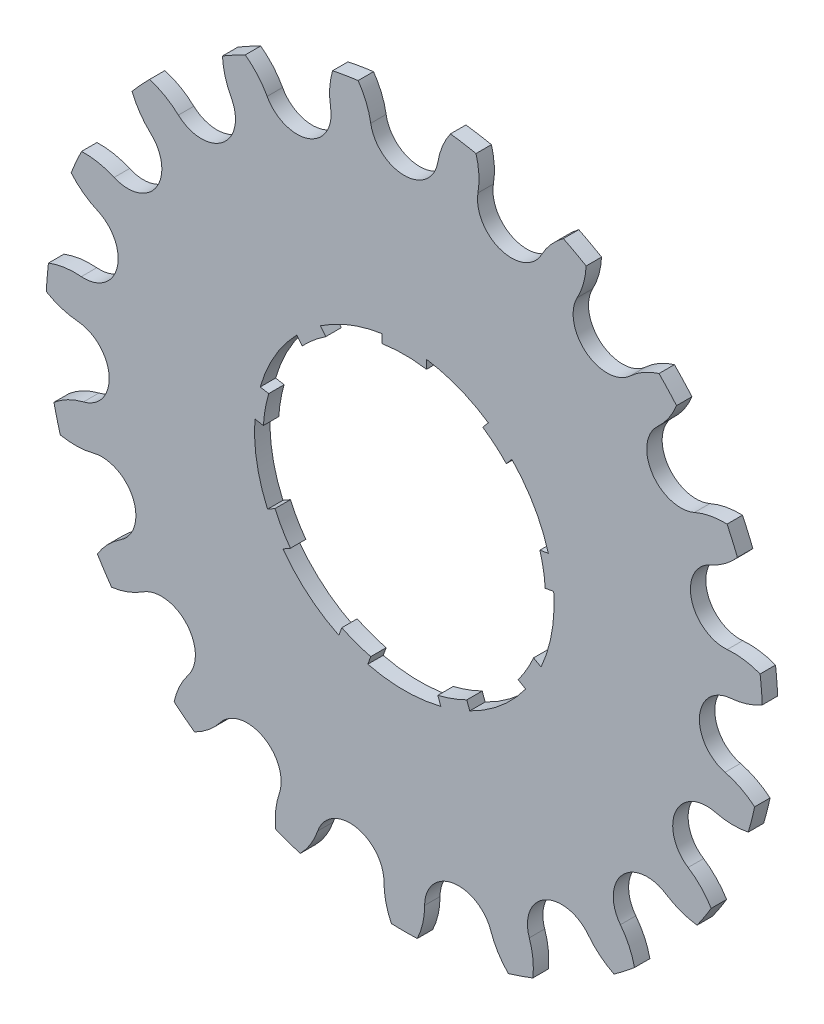
SolidWorks part; units mm, degrees
ref_plane "Alzado" through (0, 0, 0) normal (0, 0, 1) x (1, 0, 0)
ref_plane "Planta" through (0, 0, 0) normal (0, 1, 0) x (1, 0, 0)
ref_plane "Vista lateral" through (0, 0, 0) normal (1, 0, 0) x (0, 0, -1)
sketch "Sk_Disco" plane through (0, 0, 0) normal (0, 0, 1) x (1, 0, 0)
  line L0 (2.6, 17.3058) -> (2.6, 16.2939)
  line L1 (-2.6, 16.2939) -> (-2.6, 17.3058)
  line L2 (-9.8102, 14.4917) -> (-9.1638, 13.7213)
  line L3 (-11.9216, 11.4073) -> (-12.568, 12.1777)
  line L4 (-16.8302, 4.7954) -> (-15.8398, 4.6207)
  line L5 (-16.4649, 1.0754) -> (-17.4553, 1.2501)
  line L6 (-15.9751, -7.1447) -> (-15.1041, -6.6419)
  line L7 (-13.3041, -9.7596) -> (-14.1751, -10.2624)
  line L8 (-7.6451, -15.7418) -> (-7.3011, -14.7968)
  line L9 (-3.9182, -16.028) -> (-4.2622, -16.973)
  line L10 (4.2622, -16.973) -> (3.9182, -16.028)
  line L11 (7.3011, -14.7968) -> (7.6451, -15.7418)
  line L12 (14.1751, -10.2624) -> (13.3041, -9.7596)
  line L13 (15.1041, -6.6419) -> (15.9751, -7.1447)
  line L14 (17.4553, 1.2501) -> (16.4649, 1.0754)
  line L15 (15.8398, 4.6207) -> (16.8302, 4.7954)
  line L16 (12.568, 12.1777) -> (11.9216, 11.4073)
  line L17 (9.1638, 13.7213) -> (9.8102, 14.4917)
  circle A0 centre (0, 0) radius 41.8635
  arc A1 (2.6, 16.2939) -> (-2.6, 16.2939) centre (0, 0) ccw
  arc A2 (-2.6, 17.3058) -> (-9.8102, 14.4917) centre (0, 0) ccw
  arc A3 (-9.1638, 13.7213) -> (-11.9216, 11.4073) centre (0, 0) ccw
  arc A4 (-12.568, 12.1777) -> (-16.8302, 4.7954) centre (0, 0) ccw
  arc A5 (-15.8398, 4.6207) -> (-16.4649, 1.0754) centre (0, 0) ccw
  arc A6 (-17.4553, 1.2501) -> (-15.9751, -7.1447) centre (0, 0) ccw
  arc A7 (-15.1041, -6.6419) -> (-13.3041, -9.7596) centre (0, 0) ccw
  arc A8 (-14.1751, -10.2624) -> (-7.6451, -15.7418) centre (0, 0) ccw
  arc A9 (-7.3011, -14.7968) -> (-3.9182, -16.028) centre (0, 0) ccw
  arc A10 (-4.2622, -16.973) -> (4.2622, -16.973) centre (0, 0) ccw
  arc A11 (3.9182, -16.028) -> (7.3011, -14.7968) centre (0, 0) ccw
  arc A12 (7.6451, -15.7418) -> (14.1751, -10.2624) centre (0, 0) ccw
  arc A13 (13.3041, -9.7596) -> (15.1041, -6.6419) centre (0, 0) ccw
  arc A14 (15.9751, -7.1447) -> (17.4553, 1.2501) centre (0, 0) ccw
  arc A15 (16.4649, 1.0754) -> (15.8398, 4.6207) centre (0, 0) ccw
  arc A16 (16.8302, 4.7954) -> (12.568, 12.1777) centre (0, 0) ccw
  arc A17 (11.9216, 11.4073) -> (9.1638, 13.7213) centre (0, 0) ccw
  arc A18 (9.8102, 14.4917) -> (2.6, 17.3058) centre (0, 0) ccw
  dimension "D1" = 83.7269
extrude "Disco" add sketch "Sk_Disco" along normal blind 1.8
sketch "Sk_Hueco" plane through (0, 0, 0) normal (0, 0, 1) x (1, 0, 0)
  line L0 (0, 0) -> (0, 38.5796) construction
  line L1 (0, 0) -> (-12.5268, 36.4893) construction
  line L2 (0, 0) -> (12.5268, 36.4893) construction
  line L3 (0, 38.5796) -> (-12.5268, 36.4893) construction
  line L4 (0, 38.5796) -> (12.5268, 36.4893) construction
  arc A0 (-3.9208, 37.9254) -> (3.9208, 37.9254) centre (0, 38.5796) ccw
  arc A1 (-3.9208, 37.9254) -> (-7.0624, 43.2912) centre (-12.5268, 36.4893) ccw
  arc A2 (7.0624, 43.2912) -> (3.9208, 37.9254) centre (12.5268, 36.4893) ccw
  arc A3 (7.0624, 43.2912) -> (-7.0624, 43.2912) centre (0, 0) ccw
  dimension "D6" = 3.975
  dimension "D7" = 43.8635
  dimension "D1" = 38.5796
  dimension "D2" = 38.5796
  dimension "D3" = 38.5796
  dimension "D4" = 18.947
  dimension "D5" = 18.947
extrude "Hueco_diente" cut sketch "Sk_Hueco" along normal through all
ref_axis "Eje_pinon" through (0, 0, -0.09) along (0, 0, 1)
pattern_circular "Matriz_dientes" count 19 over 360 about axis through (0, 0, -0.09) along (0, 0, 1) of "Hueco_diente"
equation "\"Z\"= 19"
equation "\"p\"= 12.7"
equation "\"Dr\"= 7.75"
equation "\"e\"= 1.8"
equation "\"D\"= \"p\" / sin ( 180 / \"Z\" )"
equation "\"De\"= \"p\" * ( 0.6 + 1 / tan ( 180 / \"Z\" ) )"
equation "\"Di\"= \"D\" - \"Dr\""
equation "\"Ang\"= 360 / \"Z\""
equation "\"D1@Sk_Disco\" = \"De\""
equation "\"D1@Disco\" = \"e\""
equation "\"D1@Sk_Hueco\" = \"D\" / 2"
equation "\"D2@Sk_Hueco\" = \"D\" / 2"
equation "\"D3@Sk_Hueco\" = \"D\" / 2"
equation "\"D4@Sk_Hueco\" = \"Ang\""
equation "\"D5@Sk_Hueco\" = \"Ang\""
equation "\"D6@Sk_Hueco\" = \"Dr\" / 2 + 0.1"
equation "\"D7@Sk_Hueco\" = \"De\" / 2 + 2"
equation "\"D1@Matriz_dientes\" = \"Z\""
